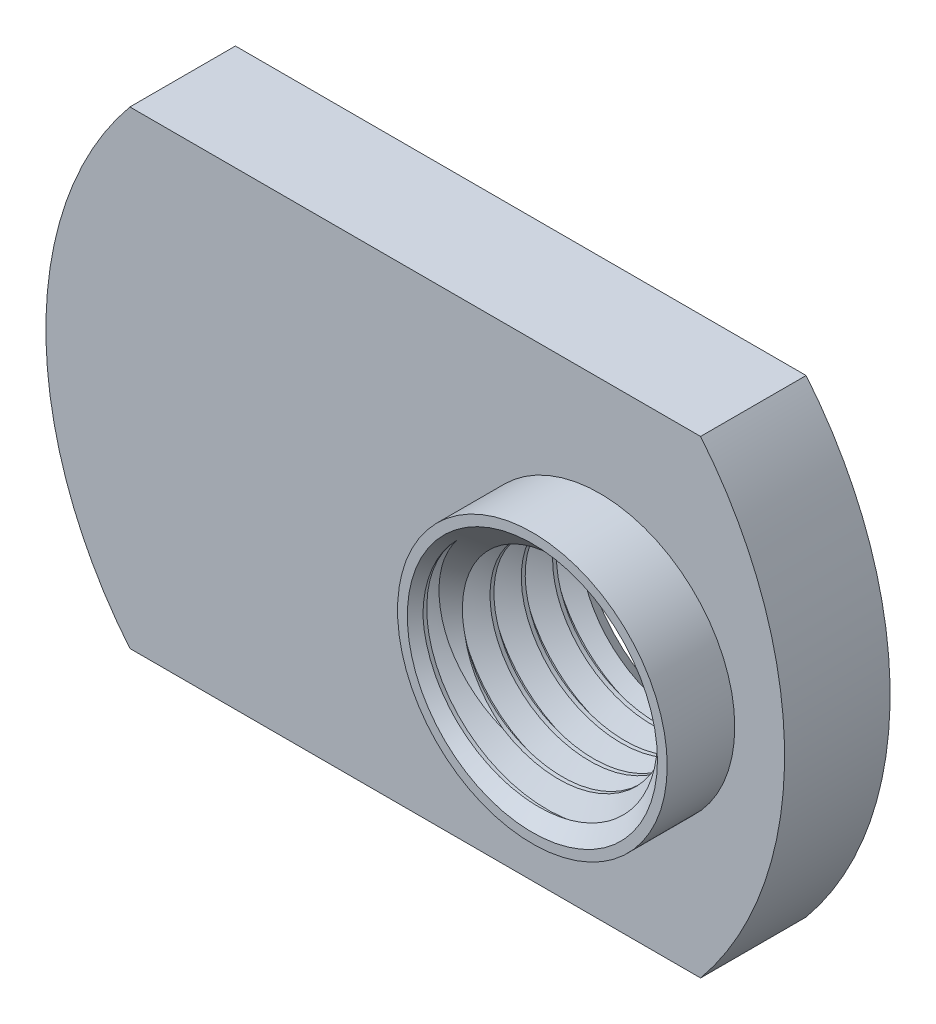
SolidWorks part; units mm, degrees
material "Plain Carbon Steel"
ref_plane "Front Plane" through (0, 0, 0) normal (0, 0, 1) x (1, 0, 0)
ref_plane "Top Plane" through (0, 0, 0) normal (0, 1, 0) x (1, 0, 0)
ref_plane "Right Plane" through (0, 0, 0) normal (1, 0, 0) x (0, 0, -1)
sketch "Sketch1" plane through (0, 0, 0) normal (0, 0, 1) x (1, 0, 0)
  line L0 (-9.6584, 7.9375) -> (9.6584, 7.9375) construction
  line L1 (-9.6584, -7.9375) -> (9.6584, -7.9375) construction
  line L2 (0, 0) -> (6.2508, 0) construction
  line L3 (6.2508, 0) -> (12.5016, 0) construction
  line L4 (-12.5016, 0) -> (12.5016, 0) construction
  arc A0 (9.6584, -7.9375) -> (9.6584, 7.9375) centre (0, 0) ccw construction
  arc A2 (-9.6584, 7.9375) -> (-9.6584, -7.9375) centre (0, 0) ccw construction
  circle A3 centre (6.2508, 0) radius 4.5641 construction
  circle A4 centre (6.2508, 0) radius 3.9688 construction
  circle A5 centre (6.2508, 0) radius 4.7625
  point P11 (6.2508, -3.9688)
  dimension "Base Length" = 25.0031
  dimension "Barrel Diameter" = 9.1281
  dimension "Thread Size" = 7.9375
  dimension "For Hole Diameter" = 9.525
  dimension "Base Width" = 15.875
sketch "Sketch9" plane through (0, 0, 0) normal (1, 0, 0) x (0, 0, -1)
  line L0 (0, 7.9375) -> (0, -7.9375) construction
  line L1 (-1.7859, -7.9375) -> (1.7859, -7.9375)
  line L2 (-1.7859, -7.9375) -> (-1.7859, 7.9375)
  line L3 (-1.7859, 7.9375) -> (1.7859, 7.9375)
  line L4 (1.7859, -7.9375) -> (1.7859, 7.9375)
  line L5 (-1.7859, 3.9688) -> (-4.0719, 3.9687) construction
  line L6 (-4.0719, 3.9687) -> (-4.0719, -3.9688) construction
  line L7 (-4.0719, -3.9688) -> (-1.7859, -3.9688) construction
  line L9 (0, 0) -> (-4.0719, 0) construction
  line L10 (-5.0641, 4.0833) -> (-4.0058, 4.0833) construction
  line L11 (-1.7859, -3.9688) -> (1.7859, -3.9688) construction
  line L12 (-4.0058, 4.0833) -> (-4.535, 3.1668) construction
  line L13 (-4.535, 3.1668) -> (-5.0641, 4.0833) construction
  line L14 (-4.0719, 3.9687) -> (-4.998, 3.9688) construction
  line L15 (-4.535, 4.0833) -> (-4.535, 3.9688) construction
  line L16 (-4.4688, 3.2813) -> (-4.6011, 3.2813) construction
  line L17 (-4.0389, 4.026) -> (-5.0311, 4.026) construction
  line L18 (-4.535, 3.2813) -> (-4.535, 3.1668) construction
  point P6 (0, 0)
  point P29 (-4.535, 4.026)
  dimension "Base Thickness" = 3.5719
  dimension "D1" = 7.9375
  dimension "Barrel Height" = 2.286
  dimension "D2" = 0.1323
  dimension "Pitch" = 1.0583
  dimension "Thread Length" = 5.8579
ref_plane "Plane1" through (6.2508, 0, 0) normal (1, 0, 0) x (0, 0, -1)
sketch "Sketch10" plane through (0, 0, 0) normal (0, 0, 1) x (1, 0, 0)
  line L0 (-9.6584, -7.9375) -> (9.6584, -7.9375) construction
  line L1 (-9.6584, 7.9375) -> (9.6584, 7.9375) construction
  line L2 (-9.6584, -7.9375) -> (9.6584, -7.9375)
  line L3 (-9.6584, 7.9375) -> (9.6584, 7.9375)
  arc A0 (-9.6584, 7.9375) -> (-9.6584, -7.9375) centre (0, 0) ccw construction
  arc A1 (9.6584, -7.9375) -> (9.6584, 7.9375) centre (0, 0) ccw construction
  arc A2 (-9.6584, 7.9375) -> (-9.6584, -7.9375) centre (0, 0) ccw
  arc A3 (9.6584, -7.9375) -> (9.6584, 7.9375) centre (0, 0) ccw
  circle A4 centre (6.2508, 0) radius 3.9688 construction
  circle A5 centre (6.2508, 0) radius 3.9688
extrude "Boss-Extrude1" add sketch "Sketch10" along normal up to vertex (1.7859 mm away) and the other way up to vertex (1.7859 mm away) up to point (0, 7.9375, 1.7859) other way up to point (0, 7.9375, -1.7859)
sketch "Sketch11" plane through (0, 0, 1.7859) normal (0, 0, 1) x (1, 0, 0)
  circle A0 centre (6.2508, 0) radius 4.5641
  circle A1 centre (6.2508, 0) radius 3.9688
  circle A2 centre (6.2508, 0) radius 4.5641 construction
  circle A3 centre (6.2508, 0) radius 3.9688 construction
extrude "Boss-Extrude2" add sketch "Sketch11" along normal up to vertex (2.286 mm away) up to point (0, 0, 4.0719)
chamfer "Chamfer1" distance 0.2646 angle 45 2 edges at (10.2195, 0, -1.7859) (10.2195, 0, 4.0719)
sketch "Sketch3" plane through (0, 0, 4.0719) normal (0, 0, -1) x (-1, 0, 0)
  circle A0 centre (-6.2508, 0) radius 3.9688 construction
  circle A1 centre (-6.2508, 0) radius 3.9688
curve "Helix/Spiral1" pitch 1.0583 height 6.9162 radius 3.9688 left hand yes centre (6.2508, 0, 4.0719) axis (0, 0, -1) start towards (0, 1, 0) parameters "pitch"=1.0583
sketch "Sketch12" plane through (6.2508, 0, 0) normal (1, 0, 0) x (0, 0, -1)
  line L0 (-4.0389, 4.026) -> (-5.0311, 4.026)
  line L1 (-5.0311, 4.026) -> (-4.6011, 3.2813)
  line L2 (-4.6011, 3.2813) -> (-4.4688, 3.2813)
  line L3 (-4.4688, 3.2813) -> (-4.0389, 4.026)
sweep "Sweep1" add profiles "Sketch12" path "Helix/Spiral1"
sketch "Sketch13" plane through (0, 0, 4.0719) normal (0, 0, 1) x (1, 0, 0)
  circle A0 centre (6.2508, 0) radius 4.2333 construction
  circle A1 centre (6.2508, 0) radius 4.2333
extrude "Cut-Extrude1" cut sketch "Sketch13" against normal through all draft 45 and the other way through all
sketch "Sketch15" plane through (0, 0, -1.7859) normal (0, 0, -1) x (-1, 0, 0)
  circle A0 centre (-6.2508, 0) radius 4.2333 construction
  circle A1 centre (-6.2508, 0) radius 4.2333
extrude "Cut-Extrude2" cut sketch "Sketch15" against normal through all draft 45 and the other way through all
equation "\"D3@Helix/Spiral1\"=\"Thread Length@Sketch9\"+\"Pitch@Sketch9\""
equation "\"D1@Sketch9\"=\"Thread Size@Sketch1\""
equation "\"D2@Sketch9\"=\"Pitch@Sketch9\"/8"
equation "\"D1@Chamfer1\"=\"Pitch@Sketch9\"/4"
equation "\"pitch@Helix/Spiral1\"=\"Pitch@Sketch9\""
